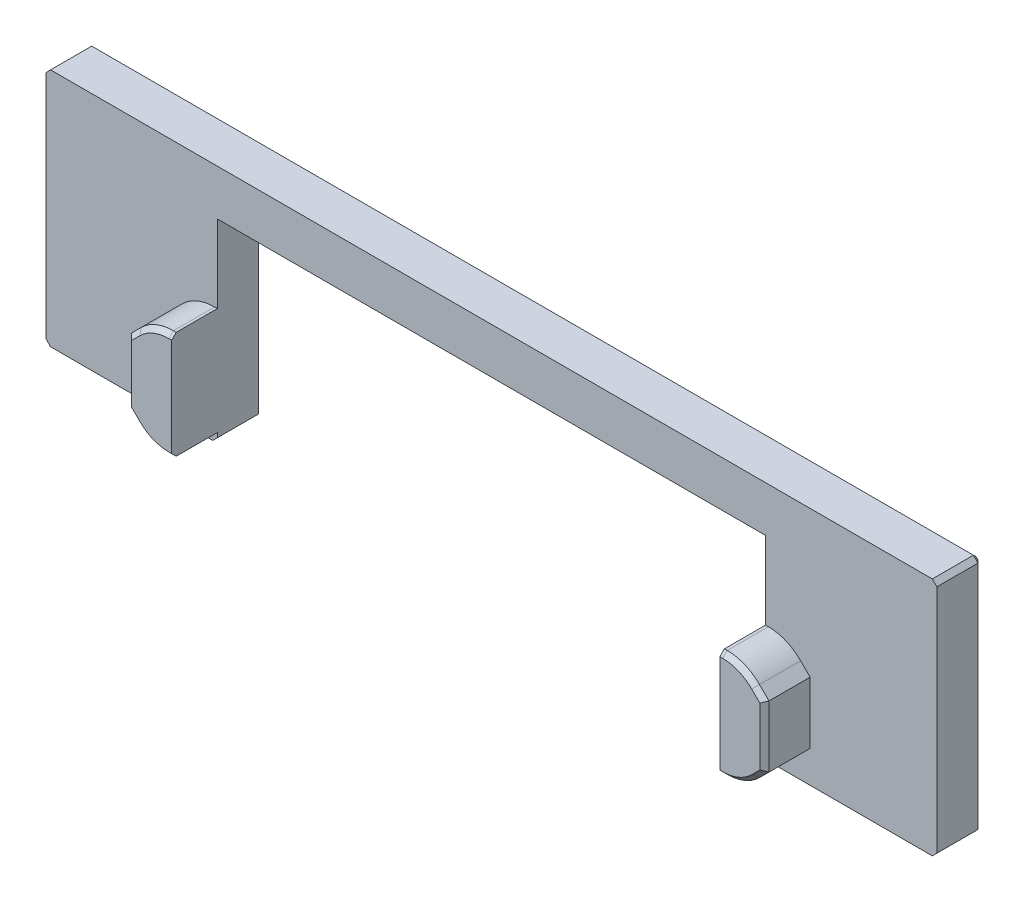
SolidWorks part; units mm, degrees
ref_plane "Front" through (0, 0, 0) normal (0, 0, 1) x (1, 0, 0)
ref_plane "Top" through (0, 0, 0) normal (0, 1, 0) x (1, 0, 0)
ref_plane "Right" through (0, 0, 0) normal (1, 0, 0) x (0, 0, -1)
sketch "Sketch1" plane through (0, 0, 0) normal (0, 0, 1) x (1, 0, 0)
  line L0 (-19.3, 5.25) -> (19.3, 5.25)
  line L5 (19.5, 5.05) -> (19.5, -5.05)
  line L6 (19.3, -5.25) -> (12.2, -5.25)
  line L7 (12, -5.05) -> (12, 3.25)
  line L8 (12, 3.25) -> (-12, 3.25)
  line L9 (-12, 3.25) -> (-12, -5.05)
  line L10 (-12.2, -5.25) -> (-19.3, -5.25)
  line L11 (-19.5, -5.05) -> (-19.5, 5.05)
  line L12 (19.5, 5.05) -> (19.5, -5.05) construction
  line L13 (19.3, -5.25) -> (12, -5.25) construction
  line L14 (19.3, 5.25) -> (-19.3, 5.25) construction
  line L15 (19.5, -5.05) -> (19.3, -5.25)
  line L16 (-12, -5.25) -> (-19.3, -5.25) construction
  line L17 (-19.5, 5.05) -> (-19.5, -5.05) construction
  line L18 (12.2, -5.25) -> (12, -5.05)
  line L19 (19.3, 5.25) -> (19.5, 5.05)
  line L20 (-19.5, 5.05) -> (-19.3, 5.25)
  line L21 (-19.3, -5.25) -> (-19.5, -5.05)
  line L22 (-12, -5.05) -> (-12.2, -5.25)
  point P0 (-19.5, 5.25)
  point P1 (19.5, 5.25)
  point P2 (19.5, -5.25)
  point P4 (12, -5.25)
  point P6 (-19.5, -5.25)
  point P13 (-12, -5.25)
extrude "Boss-Extrude1" add sketch "Sketch1" against normal blind 2
sketch "Sketch3" plane through (0, 0, 0) normal (0, 0, 1) x (1, 0, 0)
  line L3 (12, -5.05) -> (12, 3.25) construction
  line L4 (12, -4.85) -> (12, -0.15)
  line L20 (13.95, -3.85) -> (13.95, -1.15)
  line L21 (13.95, -3.85) -> (13.95, -1.15)
  line L22 (13.95, -1.15) -> (13.5358, -0.7358)
  line L23 (13.95, -1.15) -> (13.5358, -0.7358)
  line L24 (12.1216, -0.15) -> (11.3784, -0.15)
  line L25 (12.1216, -0.15) -> (12, -0.15)
  line L26 (9.9642, -0.7358) -> (9.55, -1.15)
  line L28 (9.55, -1.15) -> (9.55, -3.85)
  line L30 (9.55, -3.85) -> (9.9642, -4.2642)
  line L32 (11.3784, -4.85) -> (12.1216, -4.85)
  line L33 (12, -4.85) -> (12.1216, -4.85)
  line L34 (13.5358, -4.2642) -> (13.95, -3.85)
  line L35 (13.5358, -4.2642) -> (13.95, -3.85)
  arc A18 (13.5358, -0.7358) -> (12.1216, -0.15) centre (12.1216, -2.15) ccw
  arc A19 (13.5358, -0.7358) -> (12.1216, -0.15) centre (12.1216, -2.15) ccw
  arc A20 (11.3784, -0.15) -> (9.9642, -0.7358) centre (11.3784, -2.15) ccw
  arc A22 (9.9642, -4.2642) -> (11.3784, -4.85) centre (11.3784, -2.85) ccw
  arc A24 (12.1216, -4.85) -> (13.5358, -4.2642) centre (12.1216, -2.85) ccw
  arc A25 (12.1216, -4.85) -> (13.5358, -4.2642) centre (12.1216, -2.85) ccw
  line M20 (12, 3.25) -> (12, -5.05)
  dimension "D1" = 0
extrude "Boss-Extrude3" add sketch "Sketch3" along normal blind 2 contours L4 | L33 A25 L35 L21 L23 A19 L25 M20 region at (12.8963, -2.5, 0)
mirror "Mirror3" about plane through (0, 0, 0) normal (1, 0, 0) of "Boss-Extrude3"
chamfer "Deburs" distance 0.2 angle 45 28 edges at (12, -0.9, -2) (12.1, -5.15, -2) (15.75, -5.25, -2) (19.4, -5.15, -2) (19.5, 0, -2) (19.4, 5.15, -2) (0, 5.25, -2) (-19.4, 5.15, -2) (-19.5, 0, -2) (-19.4, -5.15, -2) (-15.75, -5.25, -2) (-12.1, -5.15, -2) (-12, -0.9, -2) (0, 3.25, -2) (-12.0608, -4.85, 2) (-13.7429, -4.0571, 2) (-12.8869, -4.6978, 2) (-13.95, -2.5, 2) (-13.7429, -0.9429, 2) (-12.0608, -0.15, 2) (-12.8869, -0.3022, 2) (12.0608, -4.85, 2) (13.7429, -4.0571, 2) (12.8869, -4.6978, 2) (13.95, -2.5, 2) (13.7429, -0.9429, 2) (12.0608, -0.15, 2) (12.8869, -0.3022, 2)
